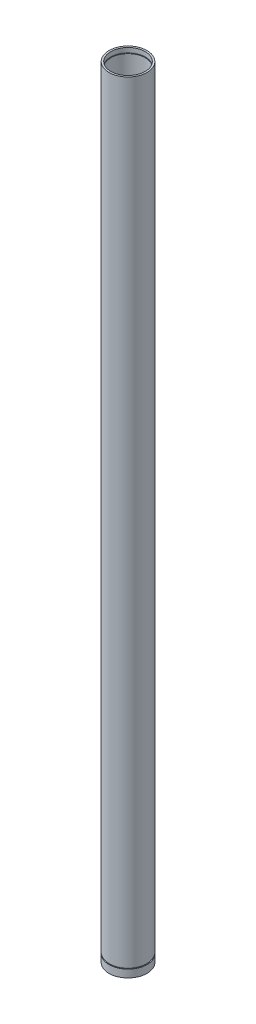
SolidWorks part; units mm, degrees
material "6061-T6 (SS)"
ref_plane "Front Plane" through (0, 0, 0) normal (0, 0, 1) x (1, 0, 0)
ref_plane "Top Plane" through (0, 0, 0) normal (0, 1, 0) x (1, 0, 0)
ref_plane "Right Plane" through (0, 0, 0) normal (1, 0, 0) x (0, 0, -1)
sketch "Sketch1" plane through (0, 0, 0) normal (0, 1, 0) x (1, 0, 0)
  circle A0 centre (0, 0) radius 27.051
  circle A1 centre (0, 0) radius 24.511
  dimension "D1" = 54.102
  dimension "D2" = 2.54
extrude "Boss-Extrude1" add sketch "Sketch1" along normal blind 1111.25
sketch "Sketch2" plane through (0, 0, 0) normal (0, 0, 1) x (1, 0, 0)
  line L0 (-27.051, 0) -> (27.051, 0) construction
  line L1 (22.733, 7.62) -> (25.273, 7.62)
  line L2 (22.733, 7.62) -> (22.733, 6.223)
  line L3 (22.733, 6.223) -> (25.273, 6.223)
  line L4 (25.273, 7.62) -> (25.273, 6.223)
  line L5 (24.511, 0) -> (24.511, 1111.25) construction
  dimension "D1" = 6.223
  dimension "D2" = 1.397
  dimension "D3" = 0.762
  dimension "D4" = 2.54
ref_axis "Axis1" through (0, 1111.25, 0) along (0, -1, 0)
revolve "Cut-Revolve1" cut sketch "Sketch2" angle 360 about axis through (0, 1111.25, 0) along (0, -1, 0)
ref_plane "Plane1" through (0, 555.625, 0) normal (0, -1, 0) x (-1, 0, 0)
mirror "Mirror1" about plane through (0, 555.625, 0) normal (0, -1, 0) of "Cut-Revolve1"
sketch "Sketch3" plane through (0, 0, 0) normal (1, 0, 0) x (0, 0, -1)
  line L1 (25.781, 12.319) -> (27.305, 12.319)
  line L2 (25.781, 12.319) -> (25.781, 10.922)
  line L3 (25.781, 10.922) -> (27.305, 10.922)
  line L4 (27.305, 12.319) -> (27.305, 10.922)
  line L5 (27.051, 0) -> (27.051, 1111.25) construction
  line L7 (-27.051, 0) -> (27.051, 0) construction
  dimension "D1" = 10.922
  dimension "D2" = 1.397
  dimension "D3" = 1.524
  dimension "D4" = 1.27
sketch "Sketch4" plane through (0, 0, 0) normal (0, 0, 1) x (1, 0, 0)
  line L0 (27.051, 0) -> (22.6695, -33.147)
  line L1 (24.511, 0) -> (20.1295, -33.147)
  line L2 (22.6695, -33.147) -> (20.1295, -33.147)
  line L3 (24.511, 0) -> (27.051, 0)
  dimension "D1" = 33.147
  dimension "D2" = 22.6695
revolve "Revolve2" [suppressed] add sketch "Sketch4" angle 360 about axis through (0, 1111.25, 0) along (0, -1, 0)
sketch "Sketch5" plane through (0, 1103.63, 0) normal (0, 1, 0) x (1, 0, 0)
  circle A0 centre (0, 0) radius 23.876
  dimension "D1" = 47.752
extrude "Boss-Extrude2" [suppressed] add sketch "Sketch5" against normal blind 12.7 separate body
sketch "Sketch6" [suppressed] plane through (0, 1103.503, 0) normal (0, 1, 0) x (1, 0, 0)
  circle A0 centre (0, 0) radius 18.034
  dimension "D1" = 36.068
extrude "Boss-Extrude4" [suppressed] add sketch "Sketch6" along normal blind 39.878 contours A0
sketch "Sketch7" [suppressed] plane through (0, 1143.381, 0) normal (0, 1, 0) x (1, 0, 0)
  circle A0 centre (0, 0) radius 7.9375
  circle A1 centre (0, 0) radius 3.175
  dimension "D1" = 6.35
  dimension "D2" = 15.875
extrude "Boss-Extrude5" [suppressed] add sketch "Sketch7" along normal blind 11.43
sketch "Sketch9" [suppressed] plane through (0, 1154.176, 0) normal (0, 1, 0) x (1, 0, 0)
  circle A0 centre (0, 0) radius 7.112
  dimension "D1" = 14.224
extrude "Boss-Extrude6" [suppressed] add sketch "Sketch9" along normal blind 9.398
sketch "Sketch10" [suppressed] plane through (0, 1102.868, 0) normal (0, 1, 0) x (1, 0, 0)
  circle A0 centre (0, 0) radius 19.05
  dimension "D1" = 38.1
extrude "Boss-Extrude7" [suppressed] add sketch "Sketch10" along normal blind 19.685
revolve "Cut-Revolve2" [suppressed] cut sketch "Sketch3" angle 360 about axis through (0, 1111.25, 0) along (0, -1, 0)
ref_plane "Plane3" [suppressed] through (0, -31.877, 0) normal (0, -1, 0) x (-1, 0, 0)
split "Split1" [suppressed] bodies to split 112
sketch "Sketch11" plane through (0, 0, 0) normal (0, 0, 1) x (1, 0, 0)
  line L0 (-27.051, 0) -> (27.051, 0) construction
  line L1 (27.7047, 10.922) -> (25.908, 10.922)
  line L2 (27.7047, 10.922) -> (27.7047, 12.446)
  line L3 (27.7047, 12.446) -> (25.908, 12.446)
  line L4 (25.908, 10.922) -> (25.908, 12.446)
  line L5 (27.051, 0) -> (27.051, 1111.25) construction
  dimension "D1" = 10.922
  dimension "D2" = 1.524
  dimension "D3" = 1.143
revolve "Cut-Revolve3" cut sketch "Sketch11" angle 360 about axis through (0, 1111.25, 0) along (0, -1, 0)
